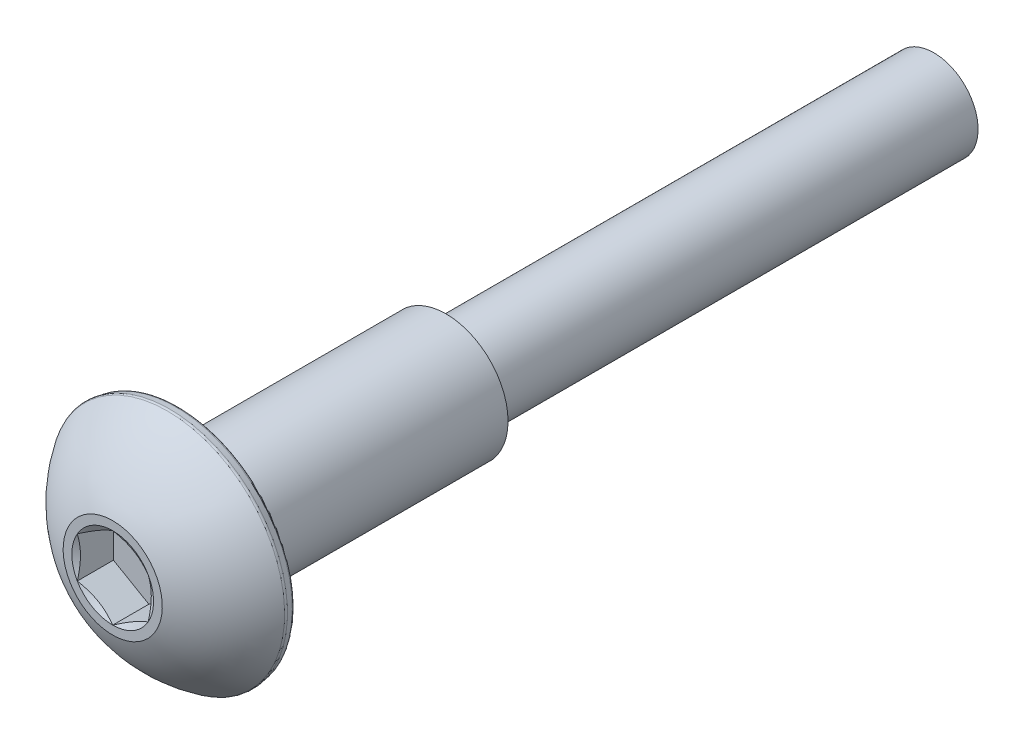
SolidWorks part; units mm, degrees
material "Alloy Steel"
ref_plane "Front Plane" through (0, 0, 0) normal (0, 0, 1) x (1, 0, 0)
ref_plane "Top Plane" through (0, 0, 0) normal (0, 1, 0) x (1, 0, 0)
ref_plane "Right Plane" through (0, 0, 0) normal (1, 0, 0) x (0, 0, -1)
sketch "Sketch1" plane through (0, 0, 0) normal (1, 0, 0) x (0, 0, -1)
  line L0 (-13.8049, 0) -> (13.8049, 0) construction
  line L1 (-13.8049, 0) -> (-13.8049, 3.9624)
  line L2 (-13.8049, 3.9624) -> (-11.5951, 3.9624)
  line L3 (-11.5951, 3.9624) -> (-11.5951, 2.0828)
  line L4 (-11.5951, 2.0828) -> (13.8049, 2.0828)
  line L5 (13.8049, 2.0828) -> (13.8049, 0)
  line L6 (13.8049, 0) -> (13.8049, -2.0828) construction
  point P2 (0, 0)
  point P4 (13.0111, 0)
  point P9 (12.6143, 2.0828)
  point P10 (12.6143, -2.0828)
  point P12 (-1.6891, 2.0828)
  point P13 (5.8801, 2.0828)
  point P14 (-3.6703, 2.0828)
  point P15 (-12.5895, 0)
  dimension "Head Height" = 2.2098
  dimension "Head Diameter" = 7.9248
  dimension "Length" = 25.4
  dimension "Screw Size Decimal Equivalent" = 4.1656
  dimension "Thread Pitch" = 0.7937
  dimension "D1" = 1.1906
  dimension "D2" = 1.2154
  dimension "D3" = 7.9248
  dimension "D4" = 7.9248
  dimension "D5" = 9.906
sketch "Sketch2" plane through (0, 0, 0) normal (0, 0, 1) x (1, 0, 0)
  line L0 (0, 2.0828) -> (0, 0) construction
  line L1 (0, 1.3748) -> (-1.1906, 0.6874)
  line L2 (-1.1906, 0.6874) -> (-1.1906, -0.6874)
  line L3 (-1.1906, -0.6874) -> (0, -1.3748)
  line L4 (0, -1.3748) -> (1.1906, -0.6874)
  line L5 (1.1906, -0.6874) -> (1.1906, 0.6874)
  line L6 (1.1906, 0.6874) -> (0, 1.3748)
  circle A0 centre (0, 0) radius 1.1906 construction
  circle A1 centre (0, 0) radius 1.6669
  point P10 (0, 1.6669)
  dimension "D1" = 3.3337
  dimension "Drive Size" = 2.3813
sketch "Sketch3" plane through (0, 0, 0) normal (1, 0, 0) x (0, 0, -1)
  line L0 (-13.8049, 0) -> (-13.8049, 1.6669)
  line L1 (-13.8049, 0) -> (-13.8049, 3.9624) construction
  line L2 (-13.8049, 3.9624) -> (-11.5951, 3.9624) construction
  line L3 (-11.9266, 3.9624) -> (-11.5951, 3.904)
  line L4 (-11.5951, 3.9624) -> (-11.5951, 2.0828) construction
  line L5 (-11.5951, 3.904) -> (-11.5951, 2.0828)
  line L6 (-13.8049, 0) -> (13.8049, 0) construction
  line L7 (-13.8049, 0) -> (13.8049, 0)
  line L8 (13.8049, 0) -> (13.8049, 1.4875)
  line L9 (13.8049, 2.0828) -> (13.8049, 0) construction
  line L10 (13.8049, 1.4875) -> (13.2096, 2.0828)
  line L11 (-11.5951, 2.0828) -> (13.8049, 2.0828) construction
  line L12 (13.2096, 2.0828) -> (-11.5951, 2.0828)
  arc A0 (-13.8049, 1.6669) -> (-11.9266, 3.9624) centre (-9.4259, 0) cw
  dimension "D1" = 0.3315
  dimension "D2" = 10
  dimension "D3" = 45
  dimension "D4" = 0.5953
revolve "Revolve1" add sketch "Sketch3" angle 360 about L7
sketch "Sketch4" plane through (0, 0, 13.8049) normal (0, 0, 1) x (1, 0, 0)
  line L0 (-1.1906, -0.6874) -> (0, -1.3748) construction
  line L1 (-1.1906, 0.6874) -> (-1.1906, -0.6874) construction
  line L2 (0, 1.3748) -> (-1.1906, 0.6874) construction
  line L3 (1.1906, 0.6874) -> (0, 1.3748) construction
  line L4 (1.1906, -0.6874) -> (1.1906, 0.6874) construction
  line L5 (0, -1.3748) -> (1.1906, -0.6874) construction
  line L6 (-1.1906, -0.6874) -> (0, -1.3748)
  line L7 (-1.1906, 0.6874) -> (-1.1906, -0.6874)
  line L8 (0, 1.3748) -> (-1.1906, 0.6874)
  line L9 (1.1906, 0.6874) -> (0, 1.3748)
  line L10 (1.1906, -0.6874) -> (1.1906, 0.6874)
  line L11 (0, -1.3748) -> (1.1906, -0.6874)
extrude "Cut-Extrude1" cut sketch "Sketch4" against normal up to vertex (1.2154 mm away) up to point (0, 0, 12.5895)
sketch "Sketch5" plane through (0, 0, 13.8049) normal (0, 0, 1) x (1, 0, 0)
  circle A0 centre (0, 0) radius 1.3748
extrude "Cut-Extrude2" cut sketch "Sketch5" against normal up to vertex (1.2154 mm away) draft 60 up to point (0, 0, 12.5895)
fillet "Fillet1" radius 0.1105 2 edges at (3.9624, 0, 11.9266) (3.904, 0, 11.5951)
split "Split1" bodies to split 106 resulting bodies 107 108 split by face at (3.8112, 0, 11.5951)
sketch "Sketch6" plane through (0, 0, -13.8049) normal (0, 0, -1) x (-1, 0, 0)
  circle A0 centre (0, 0) radius 2.0828 construction
  circle A1 centre (0, 0) radius 2.0828
curve "Helix/Spiral1" [suppressed] pitch 0.7937 height 26.1937 turns 33
sketch "Sketch7" plane through (0, 0, 0) normal (1, 0, 0) x (0, 0, -1)
  line L0 (13.7553, 2.1687) -> (14.1522, 1.4813) construction
  line L1 (14.1522, 1.4813) -> (14.549, 2.1687) construction
  line L2 (14.549, 2.1687) -> (13.7553, 2.1687) construction
  line L3 (13.7801, 2.1258) -> (14.5242, 2.1258)
  line L4 (14.5242, 2.1258) -> (14.2018, 1.5672)
  line L5 (14.2018, 1.5672) -> (14.1026, 1.5672)
  line L6 (14.1026, 1.5672) -> (13.7801, 2.1258)
  line L7 (14.1522, 1.5672) -> (14.1522, 1.4813) construction
  line L8 (13.8049, 2.0828) -> (14.4994, 2.0828) construction
  line L9 (14.1522, 2.1687) -> (14.1522, 2.0828) construction
  point P12 (14.1522, 2.1258)
  dimension "D1" = 0.7937
  dimension "D2" = 0.0992
sweep "Cut-Sweep1" [suppressed] cut profiles "Sketch7" path "Helix/Spiral1"
sketch "Sketch8" plane through (0, 0, 11.5951) normal (0, 0, -1) x (-1, 0, 0)
  circle A0 centre (0, 0) radius 2.1687
extrude "Boss-Extrude1" add sketch "Sketch8" along normal up to vertex (24.2094 mm away) draft 45 up to point (0, 2.0828, -12.6143)
ref_plane "Plane1" through (0, 0, 2.5951) normal (0, 0, -1) x (-1, 0, 0)
sketch "Sketch10" plane through (0, 0, -13.8049) normal (0, 0, -1) x (-1, 0, 0)
  circle A0 centre (0, 0) radius 3.8112
  circle A1 centre (0, 0) radius 1.4875
  circle A2 centre (0, 0) radius 1.4875 construction
  circle A3 centre (0, 0) radius 3.8112 construction
extrude "Cut-Extrude4" cut sketch "Sketch10" against normal blind 16.4
sketch "Sketch11" [suppressed] plane through (0, 0, -13.8049) normal (0, 0, -1) x (-1, 0, 0)
  circle A0 centre (0, 0) radius 1.4875
  circle A1 centre (0, 0) radius 1.4875 construction
equation "\"D1@Sketch1\"=\"Thread Pitch@Sketch1\"*1.5"
equation "\"D2@Sketch1\"=0.55*\"Head Height@Sketch1\""
equation "\"D1@Sketch2\"=\"Drive Size@Sketch2\"*1.4"
equation "\"D1@Sketch3\"=0.15*\"Head Height@Sketch1\""
equation "\"D4@Sketch3\"=0.75*\"Thread Pitch@Sketch1\""
equation "\"D1@Fillet1\"=.05*\"Head Height@Sketch1\""
equation "\"D4@Helix/Spiral1\"=\"Thread Pitch@Sketch1\""
equation "\"D2@Sketch7\"=\"D1@Sketch7\"/8"
equation "\"D1@Sketch7\"=\"Thread Pitch@Sketch1\""
equation "\"D3@Sketch1\"=\"Head Diameter@Sketch1\""
equation "\"D4@Sketch1\"=\"Head Diameter@Sketch1\""
equation "\"D5@Sketch1\"=\"D3@Sketch1\"*1.25"
